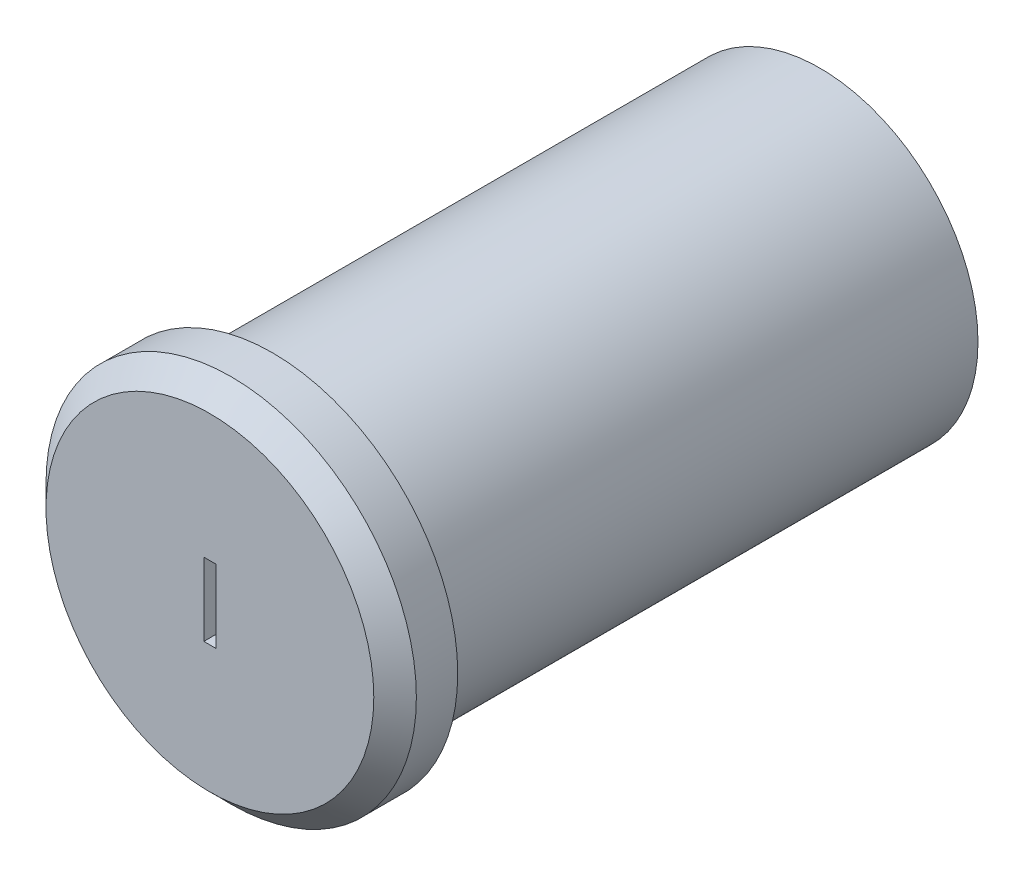
SolidWorks part; units mm, degrees
ref_plane "Front" through (0, 0, 0) normal (0, 0, 1) x (1, 0, 0)
ref_plane "Top" through (0, 0, 0) normal (0, 1, 0) x (1, 0, 0)
ref_plane "Right" through (0, 0, 0) normal (1, 0, 0) x (0, 0, -1)
sketch "Sketch1" plane through (0, 0, 0) normal (0, 0, 1) x (1, 0, 0)
  circle A0 centre (0, 0) radius 13
  dimension "D1" = 26
extrude "Boss-Extrude1" add sketch "Sketch1" against normal blind 45
sketch "Sketch2" plane through (0, 0, 0) normal (0, 0, 1) x (1, 0, 0)
  circle A0 centre (0, 0) radius 15.225
  dimension "D1" = 30.45
extrude "Boss-Extrude2" add sketch "Sketch2" along normal blind 3.4
sketch "Sketch3" plane through (0, 0, 3.4) normal (0, 0, 1) x (1, 0, 0)
  circle A1 centre (0, 0) radius 15.225
  circle A2 centre (0, 0) radius 15.225
  dimension "D1" = 0
extrude "Boss-Extrude3" add sketch "Sketch3" along normal blind 1.75 draft 45
sketch "Sketch4" plane through (0, 0, 5.15) normal (0, 0, 1) x (1, 0, 0)
  line L1 (-0.5, -3) -> (0.5, -3)
  line L2 (-0.5, -3) -> (-0.5, 3)
  line L3 (-0.5, 3) -> (0.5, 3)
  line L4 (0.5, -3) -> (0.5, 3)
  line L5 (-0.5, -3) -> (0.5, 3) construction
  line L6 (-0.5, 3) -> (0.5, -3) construction
  point P0 (0, 0)
  dimension "D1" = 1
  dimension "D2" = 6
extrude "Cut-Extrude1" cut sketch "Sketch4" against normal blind 1
sketch "Panel Cut Guide" plane through (0, 0, 0) normal (0, 0, 1) x (1, 0, 0)
  line L0 (0, 0) -> (0, -14.9606) construction
  line L3 (-2.825, -13.0988) -> (-2.825, -14.9606)
  line L4 (-2.825, -14.9606) -> (2.825, -14.9606)
  line L5 (2.825, -14.9606) -> (2.825, -13.0988)
  arc A3 (2.825, -13.0988) -> (-2.825, -13.0988) centre (0, 0) ccw
  circle A4 centre (0, 0) radius 15.225 construction
  point P1 (0, 0)
  dimension "D1" = 26.8
  dimension "D2" = 5.65
ref_plane "Panel Thickness Depth" through (0, 0, -2.2) normal (0, 0, 1) x (1, 0, 0)
